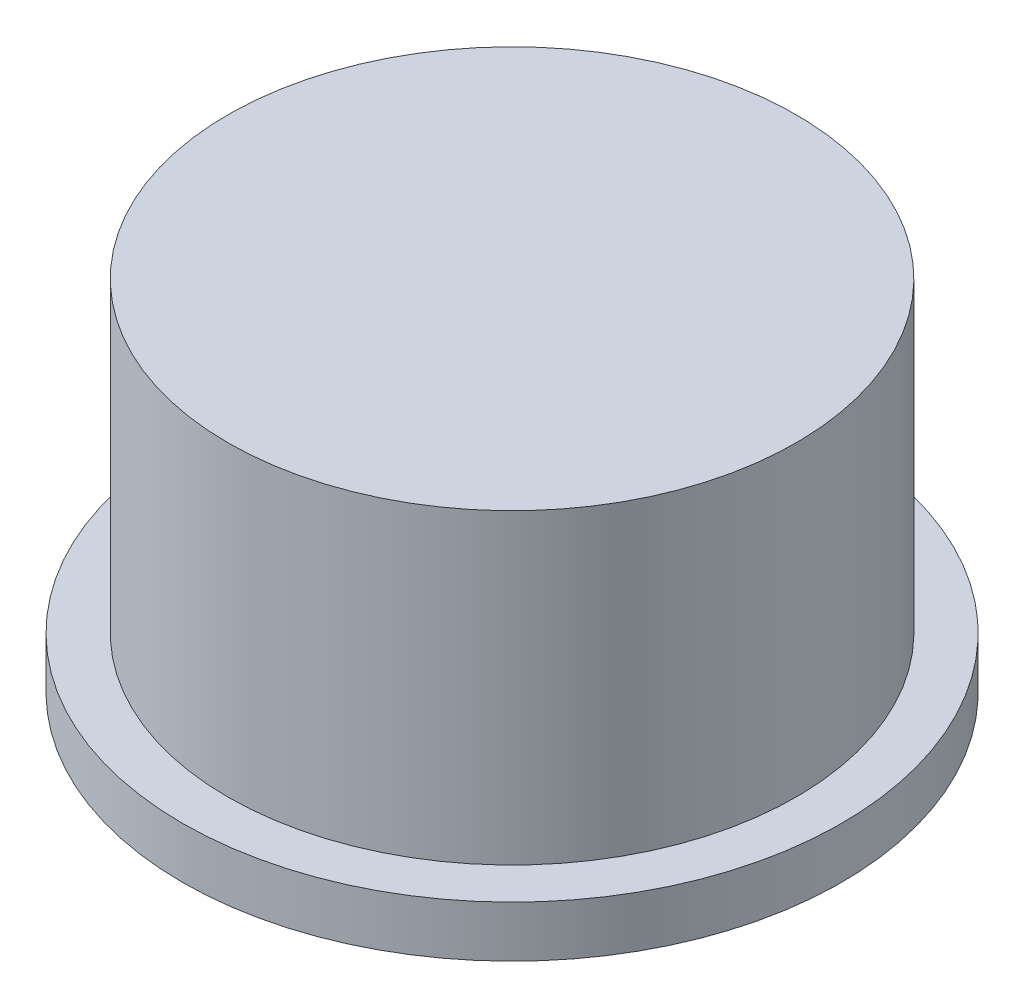
SolidWorks part; units mm, degrees
material "PVC 0.007 Plasticized"
ref_plane "Front Plane" through (0, 0, 0) normal (0, 0, 1) x (1, 0, 0)
ref_plane "Top Plane" through (0, 0, 0) normal (0, 1, 0) x (1, 0, 0)
ref_plane "Right Plane" through (0, 0, 0) normal (1, 0, 0) x (0, 0, -1)
sketch "Sketch1" plane through (0, 0, 0) normal (0, 1, 0) x (1, 0, 0)
  circle A0 centre (0, 0) radius 6.35
  circle A1 centre (0, 0) radius 7.366
  dimension "D1" = 12.7
  dimension "D2" = 14.732
extrude "Boss-Extrude1" add sketch "Sketch1" along normal blind 8.001 contours A0 region at (0, 0, 0)
extrude "Boss-Extrude2" add sketch "Sketch1<3>" along normal blind 1.143
sketch "Sketch1<3>" plane through (0, 0, 0) normal (0, 1, 0) x (1, 0, 0) same geometry as "Sketch1"
sketch "Sketch3" plane through (0, 0, 0) normal (0, 0, 1) x (1, 0, 0)
  line L1 (0, 0) -> (0, -2) construction
  line L2 (-3.5963, 0) -> (3.5963, 0)
  line L3 (-7.366, 0) -> (7.366, 0) construction
  arc A1 (3.5963, 0) -> (-3.5963, 0) centre (0, 2.2333) cw
  point P4 (0, -2)
  dimension "D2" = 4.2333
  dimension "D1" = 2
revolve "Revolve1" add sketch "Sketch3" angle 360 about L1 region at (-1.4043, -0.8188, 0)
